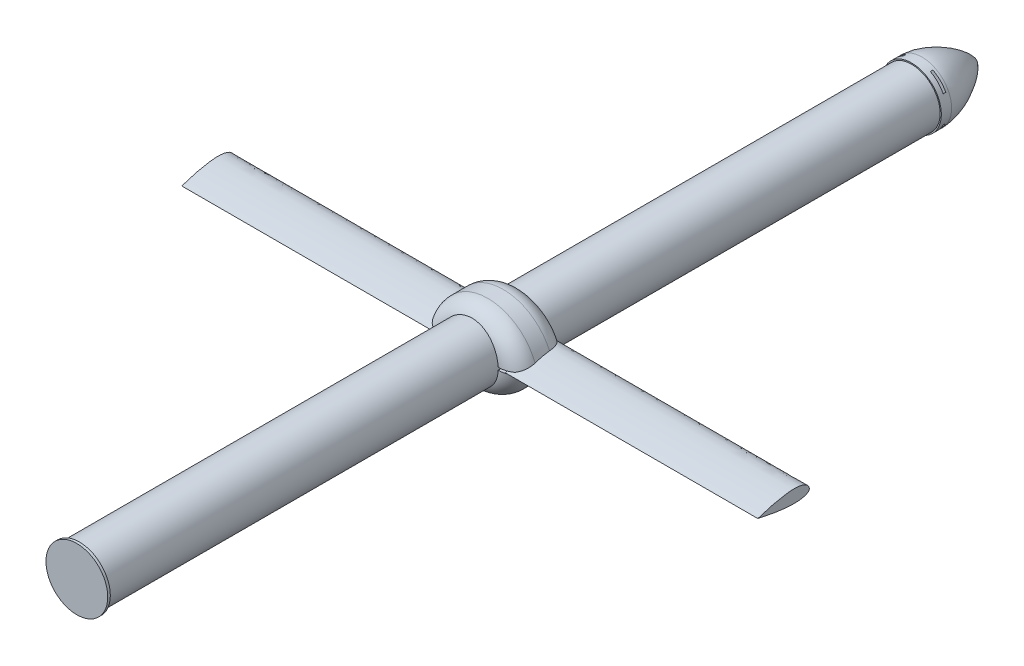
SolidWorks part; units mm, degrees
ref_plane "Front Plane" through (0, 0, 0) normal (0, 0, 1) x (1, 0, 0)
ref_plane "Top Plane" through (0, 0, 0) normal (0, 1, 0) x (1, 0, 0)
ref_plane "Right Plane" through (0, 0, 0) normal (1, 0, 0) x (0, 0, -1)
ref_plane "Plane1" through (0, 0, 10) normal (0, 0, 1) x (1, 0, 0)
sketch "Sketch1" plane through (0, 0, 10) normal (0, 0, 1) x (1, 0, 0)
  circle A0 centre (0, 0) radius 55.2
  dimension "D1" = 110.4
extrude "Boss-Extrude1" add sketch "Sketch1" along normal blind 798
sketch "Sketch3" plane through (0, 0, 808) normal (0, 0, 1) x (1, 0, 0)
  circle A0 centre (0, 0) radius 60
  dimension "D1" = 120
extrude "Boss-Extrude2" add sketch "Sketch3" along normal blind 5 contours A0
sketch "Sketch4" plane through (0, 0, 10) normal (0, 0, -1) x (-1, 0, 0)
  circle A0 centre (0, 0) radius 55.2
  dimension "D1" = 110.4
extrude "Boss-Extrude3" add sketch "Sketch4" along normal blind 20
sketch "Sketch5" plane through (0, 0, -10) normal (0, 0, -1) x (-1, 0, 0)
  circle A0 centre (0, 0) radius 55.2
  dimension "D1" = 110.4
extrude "Boss-Extrude4" add sketch "Sketch5" along normal blind 798
sketch "Sketch6" plane through (0, 0, -808) normal (0, 0, -1) x (-1, 0, 0)
  circle A0 centre (0, 0) radius 57.5
  dimension "D1" = 115
extrude "Boss-Extrude5" add sketch "Sketch6" along normal blind 10
sketch "Sketch7" plane through (0, 0, -818) normal (0, 0, -1) x (-1, 0, 0)
  line L0 (0, 25) -> (26.1895, 51.1895)
  line L1 (0, 25) -> (-26.1895, 51.1895)
  line L2 (-26.1895, 51.1895) -> (26.1895, 51.1895) construction
  circle A0 centre (0, 0) radius 57.5 construction
  arc A1 (-26.1895, 51.1895) -> (26.1895, 51.1895) centre (0, 0) cw
  circle M4 centre (0, 0) radius 57.5
  dimension "D1" = 25
  dimension "D2" = 90
extrude "Boss-Extrude6" add sketch "Sketch7" along normal blind 5 contours L2 M4 | L2 L1 L0 region at (0, 42.4596, -818) region at (0, 53.7259, -818)
pattern_circular "CirPattern1" count 4 over 360 about axis through (0, 0, -818) along (0, 0, -1) of "Boss-Extrude6"
sketch "Sketch8" plane through (0, 0, -823) normal (0, 0, -1) x (-1, 0, 0)
  circle A0 centre (0, 0) radius 57.5
  dimension "D1" = 115
extrude "Boss-Extrude7" add sketch "Sketch8" along normal blind 5
sketch "Sketch9" plane through (0, 0, 0) normal (0, 1, 0) x (1, 0, 0)
  line L0 (0, 828) -> (57.5, 828)
  line L2 (0, 931.7418) -> (0, 828)
  line L3 (57.5, 850.6026) -> (44.3947, 894.9386) construction
  line L4 (57.5, 828) -> (-57.5, 828) construction
  line L5 (44.3947, 894.9386) -> (11.0902, 931.7418) construction
  line L6 (57.5, 808) -> (57.5, 828) construction
  line L8 (57.5, 828) -> (57.5, 850.6026) construction
  line L9 (57.5, 850.6026) -> (44.3947, 894.9386) construction
  line L10 (44.3947, 894.9386) -> (11.0902, 931.7418) construction
  line L11 (11.0902, 931.7418) -> (0, 931.7418) construction
  spline S0 degree 4 poles (57.5, 828) (57.5, 850.6026) (44.3947, 894.9386) (11.0902, 931.7418) (0, 931.7418) knots 0 0 0 0 0 1 1 1 1 1
  dimension "D1" = 57.5
  dimension "D3" = 0
  dimension "D4" = 0
revolve "Revolve1" add sketch "Sketch9" angle 360 about L2
sketch "Sketch10" plane through (0, 0, 0) normal (0, 0, 1) x (1, 0, 0)
  line L0 (-94.2708, 2.5) -> (-55.1434, 2.5)
  line L1 (55.1434, 2.5) -> (94.2708, 2.5)
  arc A0 (94.2708, 2.5) -> (-94.2708, 2.5) centre (0, -25) ccw
  arc A1 (55.1434, 2.5) -> (-55.1434, 2.5) centre (0, 0) ccw
  point P2 (0, 55.2)
  point P3 (0, -25)
  point P8 (0, 73.2)
  dimension "D1" = 55.2
  dimension "D2" = 18
  dimension "D3" = 0
  dimension "D4" = 25
  dimension "D5" = 2.5
extrude "Boss-Extrude8" add sketch "Sketch10" along normal mid plane 100
fillet "Fillet1" radius 35 1 edges at (0, 73.2, 50) type face fillet first side face at (0, 33.35, 50) second side face at (0, 37.85, 0)
fillet "Fillet2" radius 35 1 edges at (0, 73.2, -50) type face fillet first side face at (0, 33.35, -50) second side face at (0, 37.85, -17.5)
mirror "Mirror2" about plane through (0, 0, 0) normal (0, 1, 0) of "Fillet1", "Fillet2", "Boss-Extrude8"
ref_plane "Plane2" through (-94.2708, 0, 0) normal (-1, 0, 0) x (0, 0, 1)
ref_plane "Plane3" through (-69.2708, 0, 0) normal (-1, 0, 0) x (0, 0, 1)
sketch "Sketch11" plane through (-69.2708, 0, 0) normal (-1, 0, 0) x (0, 0, 1)
  spline S0 degree 4 poles (-50, 0) (-49.9991, 0.3297) (-49.9705, 0.9275) (-49.8561, 1.7967) (-49.563, 2.9181) (-49.1451, 3.9907) (-48.5685, 5.0756) (-47.8077, 6.1773) (-46.7997, 7.33) (-45.5041, 8.5106) (-43.846, 9.7149) (-41.7259, 10.9292) (-39.043, 12.1146) (-35.8523, 13.1525) (-31.9595, 14.0363) (-26.8657, 14.7366) (-20.7643, 15.0274) (-14.662, 14.8248) (-8.8989, 14.3138) (-3.159, 13.5968) (1.6037, 12.8505) (6.3456, 11.9834) (11.0671, 11.0139) (14.8328, 10.183) (18.5865, 9.3015) (22.3294, 8.3726) (26.0598, 7.3994) (29.3157, 6.5093) (32.096, 5.721) (34.4127, 5.0444) (36.2537, 4.4957) (38.1107, 3.9294) (39.9289, 3.3646) (41.806, 2.7666) (43.571, 2.1956) (45.5202, 1.5463) (47.1384, 1.0009) (49.1531, 0.3002) (50.3626, -0.127) (51.915, -0.6848) (53.1337, -1.1307) (54.3912, -1.5976) (55.6393, -2.0687) (56.8855, -2.5467) (58.1291, -3.0316) (59.0597, -3.4006) (59.6792, -3.6489) (59.9887, -3.7737) knots 0 0 0 0 0 0.011046 0.020082 0.029326 0.038802 0.04958 0.06121 0.074146 0.090071 0.108265 0.129827 0.155965 0.188307 0.220649 0.263591 0.328276 0.39296 0.425303 0.457645 0.522329 0.554672 0.587014 0.619356 0.651699 0.684041 0.716383 0.748725 0.764896 0.781068 0.797239 0.81341 0.829581 0.845752 0.861923 0.878094 0.894265 0.910437 0.921632 0.932827 0.944023 0.955218 0.966414 0.977609 0.988805 1 1 1 1 1 construction
  spline S1 degree 4 poles (-50, 0) (-49.9991, 0.3297) (-49.9705, 0.9275) (-49.8561, 1.7967) (-49.563, 2.9181) (-49.1451, 3.9907) (-48.5685, 5.0756) (-47.8077, 6.1773) (-46.7997, 7.33) (-45.5041, 8.5106) (-43.846, 9.7149) (-41.7259, 10.9292) (-39.043, 12.1146) (-35.8523, 13.1525) (-31.9595, 14.0363) (-26.8657, 14.7366) (-20.7643, 15.0274) (-14.662, 14.8248) (-8.8989, 14.3138) (-3.159, 13.5968) (1.6037, 12.8505) (6.3456, 11.9834) (11.0671, 11.0139) (14.8328, 10.183) (18.5865, 9.3015) (22.3294, 8.3726) (26.0598, 7.3994) (29.3157, 6.5093) (32.096, 5.721) (34.4127, 5.0444) (36.2537, 4.4957) (38.1107, 3.9294) (39.9289, 3.3646) (41.806, 2.7666) (43.571, 2.1956) (45.5202, 1.5463) (47.1383, 1.0009) (48.7751, 0.4317) (49.5867, 0.1465) (50.0002, 0) knots 0 0 0 0 0 0.011046 0.020082 0.029326 0.038802 0.04958 0.06121 0.074146 0.090071 0.108265 0.129827 0.155965 0.188307 0.220649 0.263591 0.328276 0.39296 0.425303 0.457645 0.522329 0.554672 0.587014 0.619356 0.651699 0.684041 0.716383 0.748725 0.764896 0.781068 0.797239 0.81341 0.829581 0.845752 0.861923 0.878094 0.894265 0.910434 0.910434 0.910434 0.910434 0.910434
  spline S2 degree 4 poles (-50, 0) (-49.9997, -0.1693) (-49.984, -0.4614) (-49.9225, -0.8851) (-49.7667, -1.4356) (-49.5488, -1.9609) (-49.237, -2.5157) (-48.8032, -3.1118) (-48.1991, -3.7667) (-47.3541, -4.4954) (-46.155, -5.3152) (-44.4798, -6.2106) (-42.1095, -7.1807) (-39.0529, -8.0963) (-34.5704, -9.0396) (-28.792, -9.73) (-22.0225, -10.0275) (-14.3514, -9.8891) (-7.6531, -9.4657) (-1.9252, -8.9399) (3.7915, -8.3061) (9.4968, -7.5766) (15.1885, -6.7461) (20.8667, -5.8302) (25.5899, -5.0142) (29.3624, -4.3307) (32.6596, -3.7058) (35.4801, -3.1515) (37.5962, -2.7233) (39.0005, -2.4341) (40.1811, -2.1872) (41.104, -1.9926) (42.3051, -1.7354) (43.6554, -1.4439) (45.3898, -1.0596) (47.1027, -0.6748) (49.4365, -0.1347) (51.1191, 0.2637) (53.9947, 0.9599) (55.7889, 1.4169) (57.9207, 1.9617) (59.0082, 2.2534) (59.6995, 2.4359) (59.9984, 2.5166) knots 0 0 0 0 0 0.005887 0.010193 0.014867 0.019889 0.025655 0.032315 0.040498 0.050865 0.064448 0.082823 0.106556 0.139954 0.175459 0.242256 0.309053 0.375849 0.442646 0.476045 0.509443 0.57624 0.643037 0.676435 0.709833 0.743232 0.77663 0.793329 0.810028 0.818378 0.826728 0.835077 0.843427 0.860126 0.876825 0.893524 0.910224 0.932668 0.955112 0.977556 0.988778 1 1 1 1 1 construction
  spline S3 degree 4 poles (-50, 0) (-49.9997, -0.1693) (-49.984, -0.4614) (-49.9225, -0.8851) (-49.7667, -1.4356) (-49.5488, -1.9609) (-49.237, -2.5157) (-48.8032, -3.1118) (-48.1991, -3.7667) (-47.3541, -4.4954) (-46.155, -5.3152) (-44.4798, -6.2106) (-42.1095, -7.1807) (-39.0529, -8.0963) (-34.5704, -9.0396) (-28.792, -9.73) (-22.0225, -10.0275) (-14.3514, -9.8891) (-7.6531, -9.4657) (-1.9252, -8.9399) (3.7915, -8.3061) (9.4968, -7.5766) (15.1885, -6.7461) (20.8667, -5.8302) (25.5899, -5.0142) (29.3624, -4.3307) (32.6596, -3.7058) (35.4801, -3.1515) (37.5962, -2.7233) (39.0005, -2.4341) (40.1811, -2.1872) (41.104, -1.9926) (42.3051, -1.7354) (43.6554, -1.4439) (45.3898, -1.0596) (47.1027, -0.6748) (48.7145, -0.3018) (49.5756, -0.1002) (50.0002, 0) knots 0 0 0 0 0 0.005887 0.010193 0.014867 0.019889 0.025655 0.032315 0.040498 0.050865 0.064448 0.082823 0.106556 0.139954 0.175459 0.242256 0.309053 0.375849 0.442646 0.476045 0.509443 0.57624 0.643037 0.676435 0.709833 0.743232 0.77663 0.793329 0.810028 0.818378 0.826728 0.835077 0.843427 0.860126 0.876825 0.893524 0.910224 0.910224 0.910224 0.910224 0.910224
  dimension "D1" = 50
extrude "Boss-Extrude9" add sketch "Sketch11" along normal blind 490
mirror "Mirror3" about plane through (0, 0, 0) normal (1, 0, 0) of "Boss-Extrude9"
